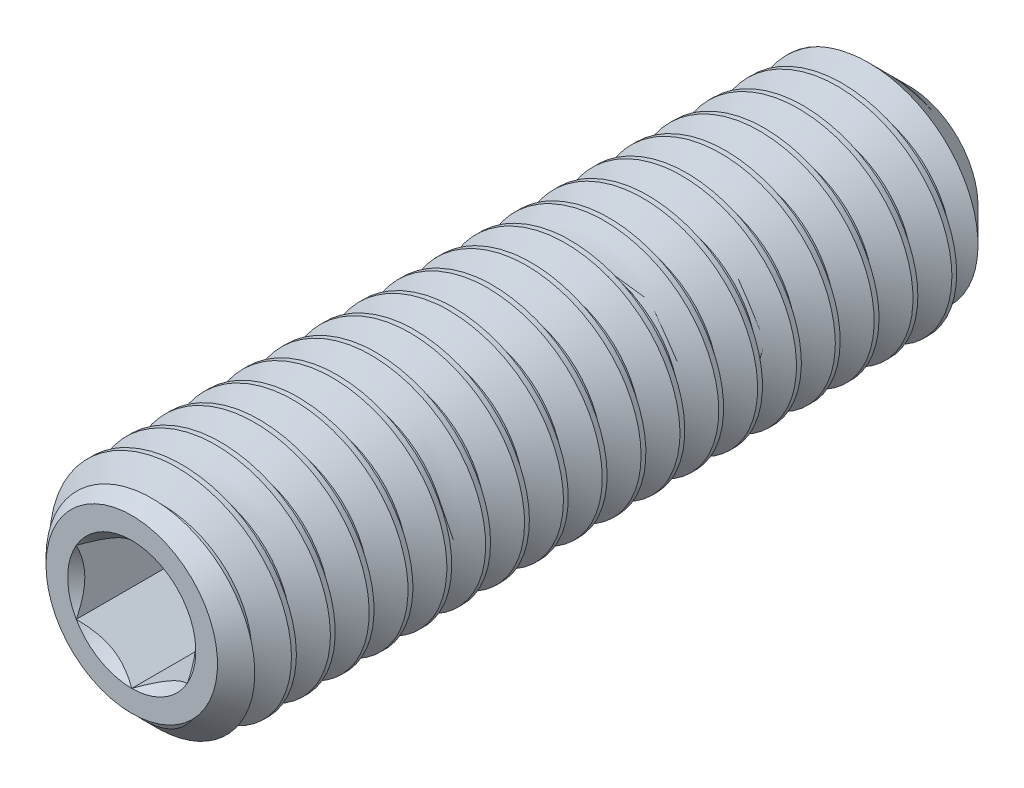
SolidWorks part; units mm, degrees
ref_plane "Front Plane" through (0, 0, 0) normal (0, 0, 1) x (1, 0, 0)
ref_plane "Top Plane" through (0, 0, 0) normal (0, 1, 0) x (1, 0, 0)
ref_plane "Right Plane" through (0, 0, 0) normal (1, 0, 0) x (0, 0, -1)
sketch "Sketch1" plane through (0, 0, 0) normal (1, 0, 0) x (0, 0, -1)
  line L0 (-7, 0) -> (7, 0) construction
  line L1 (-7, -2) -> (-7, 2) construction
  line L2 (-7, -1) -> (-7, 1) construction
  line L3 (-7, 2) -> (7, 2) construction
  line L4 (7, 2) -> (7, 0) construction
  line L5 (-7.6562, 2.0758) -> (-6.9562, 2.0758)
  line L6 (-6.9562, 2.0758) -> (-7.3062, 1.4696)
  line L7 (-7.3062, 1.4696) -> (-7.6562, 2.0758)
  line L8 (-7.3062, 1.4696) -> (-7.3062, 1.5453)
  line L9 (-7.3062, 2.0758) -> (-7.3062, 2)
  line L10 (-7.6125, 2) -> (-7, 2)
  line L11 (-7.6344, 2.0379) -> (-6.9781, 2.0379)
  line L12 (-7.35, 1.5453) -> (-7.2625, 1.5453)
  line L13 (-7, 1.5453) -> (-6.5453, 2) construction
  line L14 (-7, -1.5453) -> (-6.5453, -2) construction
  line L15 (6.25, 2) -> (7, 1.25) construction
  point P3 (-5.95, -2)
  point P4 (0, 0)
  point P8 (-7, 0)
  point P11 (-7, 0)
  point P18 (-4.5, 0)
  point P21 (-7.3062, 2)
  point P24 (-7.3062, 2.0379)
  point P27 (-7.3062, 1.5453)
  dimension "Length" = 14
  dimension "Thread Size" = 4
  dimension "Drive Size" = 2
  dimension "Thread Pitch" = 0.7
  dimension "D1" = 0.0875
  dimension "D2" = 1.05
  dimension "Drive Depth" = 2.5
  dimension "Drive Side Chamfer Angle" = 90
  dimension "Bottom Chamfer Angle" = 45
  dimension "Bottom Chamfer Diameter" = 2.5
sketch "Sketch2" plane through (0, 0, 0) normal (1, 0, 0) x (0, 0, -1)
  line L0 (6.25, 2) -> (7, 1.25) construction
  line L1 (-7, 0) -> (7, 0)
  line L2 (-7, 0) -> (-7, 1.5453)
  line L3 (-6.5453, 2) -> (6.25, 2)
  line L4 (7, 0) -> (7, 1.25)
  line L5 (-7, 1.5453) -> (-6.5453, 2) construction
  line L6 (6.25, 2) -> (7, 1.25)
  line L7 (-7, 1.5453) -> (-6.5453, 2)
revolve "Revolve1" add sketch "Sketch2" angle 360 about L1
sketch "Sketch3" plane through (0, 0, 7) normal (0, 0, 1) x (1, 0, 0)
  line L0 (0, -1) -> (0, 1) construction
  line L1 (0, 1.1547) -> (-1, 0.5774)
  line L2 (-1, 0.5774) -> (-1, -0.5774)
  line L3 (-1, -0.5774) -> (0, -1.1547)
  line L4 (0, -1.1547) -> (1, -0.5774)
  line L5 (1, -0.5774) -> (1, 0.5774)
  line L6 (1, 0.5774) -> (0, 1.1547)
  line L7 (0, -2) -> (0, 2) construction
  circle A0 centre (0, 0) radius 1 construction
extrude "Cut-Extrude1" cut sketch "Sketch3" against normal up to vertex (7 mm away) up to point (0, 0, 0)
sketch "Sketch4" plane through (0, 0, 0) normal (0, 0, 1) x (1, 0, 0)
  line L0 (-1, 0.5774) -> (-1, -0.5774) construction
  circle A0 centre (0, 0) radius 1
extrude "Cut-Extrude2" cut sketch "Sketch4" against normal through all draft 60
sketch "Sketch5" plane through (0, 0, 7) normal (0, 0, 1) x (1, 0, 0)
  line L0 (0, -2) -> (0, 2) construction
  circle A0 centre (0, 0) radius 1.1547
extrude "Cut-Extrude3" cut sketch "Sketch5" against normal blind 2.5 draft 45
sketch "Sketch6" plane through (0, 0, 7) normal (0, 0, 1) x (1, 0, 0)
  line L0 (0, -2) -> (0, 2) construction
  circle A0 centre (0, 0) radius 2
curve "Helix/Spiral1" pitch 0.7 height 14.7 radius 2 centre (0, 0, 7) axis (0, 0, -1) start towards (0, 1, 0)
sketch "Sketch7" plane through (0, 0, 0) normal (1, 0, 0) x (0, 0, -1)
  line L0 (-7.6344, 2.0379) -> (-6.9781, 2.0379)
  line L1 (-6.9781, 2.0379) -> (-7.2625, 1.5453)
  line L2 (-7.2625, 1.5453) -> (-7.35, 1.5453)
  line L3 (-7.35, 1.5453) -> (-7.6344, 2.0379)
sweep "Cut-Sweep1" cut profiles "Sketch7" path "Helix/Spiral1"
equation "\"D1@Sketch1\"=\"Thread Pitch@Sketch1\"/8"
equation "\"D1\"= \"Length@Sketch1\" * .438"
equation "\"D4@Helix/Spiral1\"=\"Thread Pitch@Sketch1\""
equation "\"D3@Helix/Spiral1\"=\"Thread Pitch@Sketch1\"+\"Length@Sketch1\""
equation "\"D2@Sketch1\"=\"Thread Pitch@Sketch1\"*1.5"
equation "\"D1@Cut-Extrude3\"=\"Drive Depth@Sketch1\""
